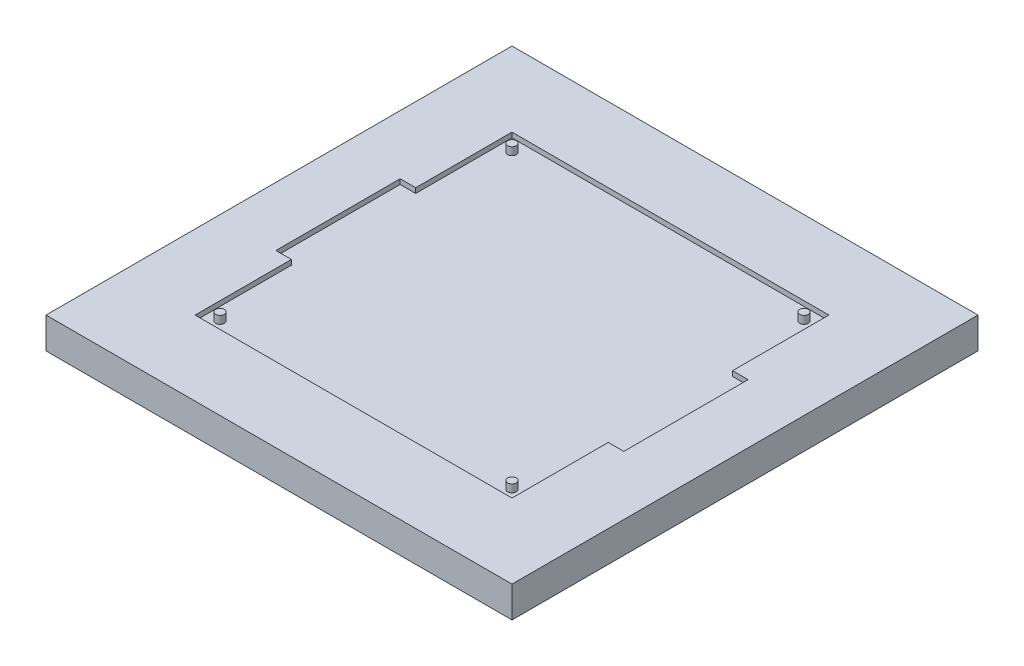
SolidWorks part; units mm, degrees
ref_plane "Front Plane" through (0, 0, 0) normal (0, 0, 1) x (1, 0, 0)
ref_plane "Top Plane" through (0, 0, 0) normal (0, 1, 0) x (1, 0, 0)
ref_plane "Right Plane" through (0, 0, 0) normal (1, 0, 0) x (0, 0, -1)
sketch "Sketch1" plane through (0, 0, 0) normal (0, 1, 0) x (1, 0, 0)
  line L1 (0, 0) -> (150, 0)
  line L2 (0, 0) -> (0, 150)
  line L3 (0, 150) -> (150, 150)
  line L4 (150, 0) -> (150, 150)
  dimension "D1" = 150
  dimension "D2" = 150
extrude "Boss-Extrude1" add sketch "Sketch1" along normal blind 10
sketch "Sketch3" plane through (0, 10, 0) normal (0, 1, 0) x (1, 0, 0)
  line L0 (0, 150) -> (0, 0) construction
  line L1 (24, 126) -> (126, 126)
  line L2 (24, 126) -> (24, 24)
  line L3 (24, 24) -> (126, 24)
  line L4 (126, 126) -> (126, 24)
  line L5 (0, 0) -> (150, 0) construction
  dimension "D1" = 102
  dimension "D2" = 102
  dimension "D3" = 24
  dimension "D4" = 24
extrude "Cut-Extrude1" cut sketch "Sketch3" against normal blind 1.6
sketch "Sketch4" plane through (0, 8.4, 0) normal (0, 1, 0) x (1, 0, 0)
  line L0 (126, 126) -> (24, 126) construction
  line L2 (126, 24) -> (126, 126) construction
  line L3 (24, 126) -> (24, 24) construction
  circle A0 centre (28, 122) radius 1.4
  circle A1 centre (122, 122) radius 1.4
  circle A2 centre (28, 28) radius 1.4
  circle A3 centre (122, 28) radius 1.4
  point P8 (0, 0)
  dimension "D1" = 2.8
  dimension "D2" = 2.8
  dimension "D4" = 2.8
  dimension "D6" = 2.8
  dimension "D3" = 94
  dimension "D5" = 94
  dimension "D7" = 94
  dimension "D8" = 94
  dimension "D9" = 4
  dimension "D10" = 4
  dimension "D11" = 4
  dimension "D12" = 4
extrude "Boss-Extrude3" add sketch "Sketch4" along normal blind 2.5
sketch "Sketch11" plane through (0, 10, 0) normal (0, 1, 0) x (1, 0, 0)
  line L0 (24, 126) -> (24, 24) construction
  line L1 (24, 95) -> (19, 95)
  line L2 (24, 95) -> (24, 55)
  line L3 (24, 55) -> (19, 55)
  line L4 (19, 95) -> (19, 55)
  line L5 (24, 24) -> (126, 24) construction
  line L8 (126, 24) -> (126, 126) construction
  line L9 (126, 55) -> (131, 55)
  line L10 (126, 55) -> (126, 95)
  line L11 (126, 95) -> (131, 95)
  line L12 (131, 55) -> (131, 95)
  line L13 (126, 126) -> (24, 126) construction
  dimension "D1" = 40
  dimension "D2" = 31
  dimension "D3" = 5
  dimension "D4" = 5
  dimension "D5" = 31
  dimension "D6" = 40
extrude "Cut-Extrude3" cut sketch "Sketch11" against normal blind 1.6
